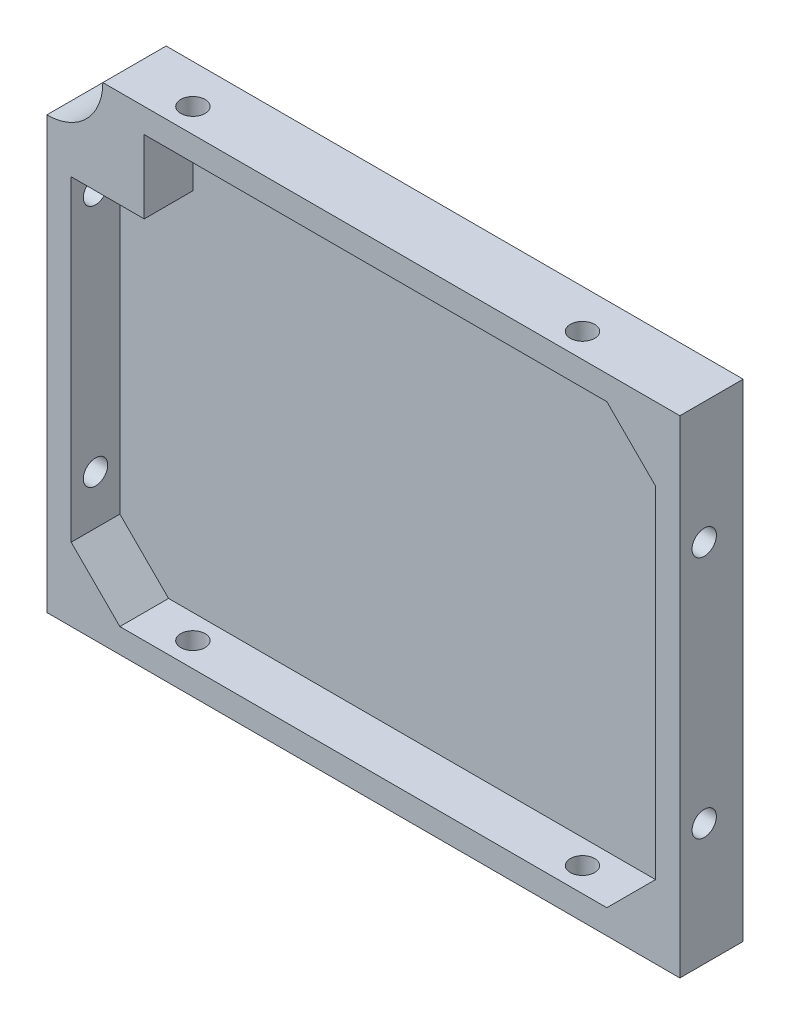
SolidWorks part; units mm, degrees
ref_plane "Plan de face" through (0, 0, 0) normal (0, 0, 1) x (1, 0, 0)
ref_plane "Plan de dessus" through (0, 0, 0) normal (0, 1, 0) x (1, 0, 0)
ref_plane "Plan de droite" through (0, 0, 0) normal (1, 0, 0) x (0, 0, -1)
sketch "Esquisse1" plane through (0, 0, 0) normal (0, 0, 1) x (1, 0, 0)
  line L0 (44.1184, 33.7284) -> (54.1184, 33.7284)
  line L1 (-75.8816, 33.7284) -> (44.1184, 33.7284)
  line L2 (-75.8816, 33.7284) -> (-75.8816, -66.2716)
  line L3 (-75.8816, -66.2716) -> (54.1184, -66.2716)
  line L4 (54.1184, 23.7284) -> (54.1184, -66.2716)
  line L5 (54.1184, 33.7284) -> (54.1184, 23.7284)
  point P6 (54.1184, 33.7284)
  dimension "D1" = 130
  dimension "D2" = 100
extrude "Boss.-Extru.1" add sketch "Esquisse1" along normal blind 13
shell "Coque1" thickness 5 removed face at (-10.8816, -16.2716, 13)
sketch "Esquisse2" plane through (-75.8816, 0, 0) normal (-1, 0, 0) x (0, 0, 1)
  line L0 (13, 33.7284) -> (13, -66.2716) construction
  line L1 (13, 33.7284) -> (0, 33.7284) construction
  line L2 (13, -66.2716) -> (0, -66.2716) construction
  circle A0 centre (8, 8.7284) radius 2.5
  circle A1 centre (8, -41.2716) radius 2.5
  dimension "D1" = 5
  dimension "D2" = 5
  dimension "D3" = 5
  dimension "D4" = 5
  dimension "D5" = 25
  dimension "D6" = 25
extrude "Enlèv. mat.-Extru.1" cut sketch "Esquisse2" against normal up to surface (130 mm away) contours A1 | A0 region at (-75.8816, -41.2716, 8) up to face at (54.1184, -16.2716, 6.5)
sketch "Esquisse3" plane through (0, -66.2716, 0) normal (0, -1, 0) x (1, 0, 0)
  line L0 (-75.8816, 13) -> (54.1184, 13) construction
  line L2 (54.1184, 13) -> (54.1184, 0) construction
  line L3 (-75.8816, 13) -> (-75.8816, 0) construction
  circle A0 centre (-50.8816, 8) radius 2.5
  circle A1 centre (29.1184, 8) radius 2.5
  dimension "D1" = 5
  dimension "D2" = 5
  dimension "D3" = 5
  dimension "D4" = 5
  dimension "D5" = 25
  dimension "D6" = 25
extrude "Enlèv. mat.-Extru.2" cut sketch "Esquisse3" against normal up to surface (100 mm away) up to face at (-10.8816, 33.7284, 6.5)
sketch "Esquisse4" plane through (0, 0, 3) normal (0, 0, 1) x (1, 0, 0)
  line L0 (-60.8816, -61.2716) -> (-70.8816, -51.2716)
  line L1 (49.1184, 28.7284) -> (-70.8816, 28.7284) construction
  line L3 (-70.8816, 28.7284) -> (-70.8816, -61.2716) construction
  line L4 (-70.8816, -51.2716) -> (-70.8816, -61.2716)
  line L5 (49.1184, 28.7284) -> (49.1184, 18.7284)
  line L6 (49.1184, -61.2716) -> (49.1184, 28.7284) construction
  line L7 (49.1184, 18.7284) -> (39.1184, 28.7284)
  line L8 (39.1184, 28.7284) -> (49.1184, 28.7284)
  line L9 (49.1184, 28.7284) -> (-70.8816, 28.7284) construction
  line L10 (49.1184, -61.2716) -> (49.1184, -51.2716)
  line L11 (49.1184, -51.2716) -> (39.1184, -61.2716)
  line L12 (-70.8816, -61.2716) -> (49.1184, -61.2716) construction
  line L13 (39.1184, -61.2716) -> (49.1184, -61.2716)
  line L14 (-70.8816, 28.7284) -> (-70.8816, -61.2716) construction
  line L15 (-70.8816, -61.2716) -> (-60.8816, -61.2716)
  line L17 (-55.8816, 28.7284) -> (-55.8816, 13.7284)
  line L18 (-55.8816, 13.7284) -> (-70.8816, 13.7284)
  line L19 (-70.8816, 13.7284) -> (-70.8816, 28.7284)
  line L20 (-70.8816, 28.7284) -> (-55.8816, 28.7284)
  dimension "D1" = 10
  dimension "D2" = 10
  dimension "D3" = 10
  dimension "D4" = 10
  dimension "D5" = 10
  dimension "D6" = 10
  dimension "D7" = 15
  dimension "D8" = 15
extrude "Boss.-Extru.2" add sketch "Esquisse4" along normal up to surface (10 mm away) up to face at (-10.8816, -16.2716, 13)
sketch "Esquisse6" plane through (0, 0, 13) normal (0, 0, 1) x (1, 0, 0)
  circle A0 centre (-75.8816, 33.7284) radius 11.5
  dimension "D1" = 23
extrude "Enlèv. mat.-Extru.4" cut sketch "Esquisse6" against normal up to surface (13 mm away) up to face at (-10.8816, -16.2716, 0)
